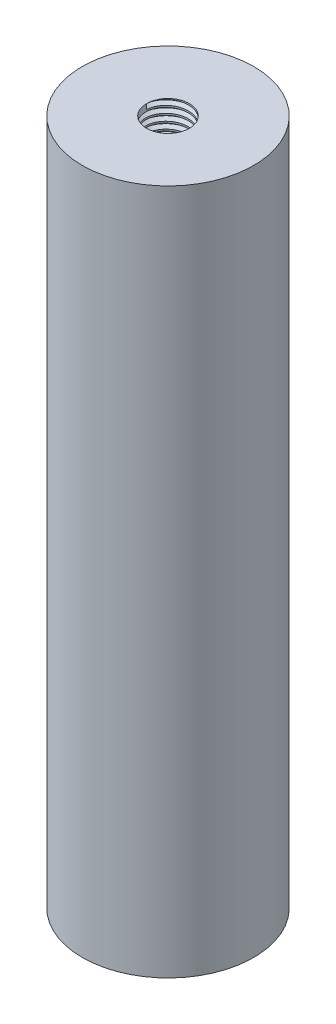
SolidWorks part; units mm, degrees
ref_plane "Front Plane" through (0, 0, 0) normal (0, 0, 1) x (1, 0, 0)
ref_plane "Top Plane" through (0, 0, 0) normal (0, 1, 0) x (1, 0, 0)
ref_plane "Right Plane" through (0, 0, 0) normal (1, 0, 0) x (0, 0, -1)
sketch "Sketch1" plane through (0, 0, 0) normal (0, 1, 0) x (1, 0, 0)
  circle A0 centre (0, 0) radius 10
extrude "Boss-Extrude1" add sketch "Sketch1" along normal blind 80
sketch "Sketch2" plane through (0, 0, 0) normal (0, -1, 0) x (1, 0, 0)
  circle A0 centre (0, 0) radius 2.5
extrude "Cut-Extrude1" cut sketch "Sketch2" against normal blind 20
sketch "Sketch3" plane through (0, 80, 0) normal (0, 1, 0) x (1, 0, 0)
  circle A0 centre (0, 0) radius 2.5
extrude "Cut-Extrude2" cut sketch "Sketch3" against normal blind 20
thread "Thread1" pitch 0.8 method cut profile "Thread Profile1" start angle 0, offset 0, length 0, pitch 0.8, diameter 5
ref_plane "Plane1" through (2.5, 0, 0) normal (0, 0, 1) x (1, 0, 0)
sketch "Thread Profile1" plane through (2.5, 0, 0) normal (0, 0, 1) x (1, 0, 0)
  line L0 (0, 0) -> (0, 0.8) construction
  line L1 (0, 0) -> (0.433, 0.25)
  line L2 (0.433, 0.25) -> (0.433, 0.35)
  line L3 (0.433, 0.35) -> (0, 0.6)
  line L4 (0.433, 0.3) -> (0, 0.3) construction
  line L11 (0, 0) -> (0, 0.6)
  point P2 (0, 0)
  dimension "Pitch" = 0.8
  dimension "Profile_Angle" = 60
  dimension "Profile_Land" = 0.1
  dimension "Profile_Height" = 0.433
thread "Thread2" pitch 0.8 method cut profile "Thread Profile2" start angle 0, offset 0, length 0, pitch 0.8, diameter 5
ref_plane "Plane2" through (-2.5, 80, 0) normal (0, 0, 1) x (-1, 0, 0)
sketch "Thread Profile2" plane through (-2.5, 80, 0) normal (0, 0, 1) x (-1, 0, 0)
  line L0 (0, 0) -> (0, 0.8) construction
  line L1 (0, 0) -> (0.433, 0.25)
  line L2 (0.433, 0.25) -> (0.433, 0.35)
  line L3 (0.433, 0.35) -> (0, 0.6)
  line L4 (0.433, 0.3) -> (0, 0.3) construction
  line L11 (0, 0) -> (0, 0.6)
  point P2 (0, 0)
  dimension "Pitch" = 0.8
  dimension "Profile_Angle" = 60
  dimension "Profile_Land" = 0.1
  dimension "Profile_Height" = 0.433
